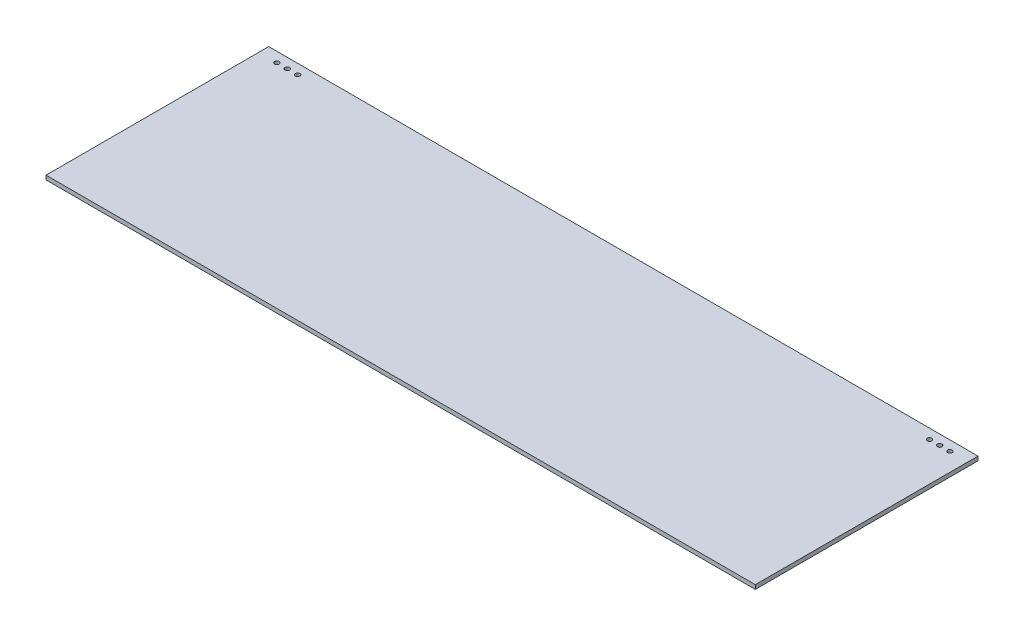
SolidWorks part; units mm, degrees
ref_plane "Front Plane" through (0, 0, 0) normal (0, 0, 1) x (1, 0, 0)
ref_plane "Top Plane" through (0, 0, 0) normal (0, 1, 0) x (1, 0, 0)
ref_plane "Right Plane" through (0, 0, 0) normal (1, 0, 0) x (0, 0, -1)
sketch "Sketch1" plane through (0, 0, 0) normal (0, 0, 1) x (1, 0, 0)
  line L1 (-273.05, -1.5875) -> (273.05, -1.5875)
  line L2 (-273.05, -1.5875) -> (-273.05, 1.5875)
  line L3 (-273.05, 1.5875) -> (273.05, 1.5875)
  line L4 (273.05, -1.5875) -> (273.05, 1.5875)
  line L5 (-273.05, -1.5875) -> (273.05, 1.5875) construction
  line L6 (-273.05, 1.5875) -> (273.05, -1.5875) construction
  point P0 (0, 0)
  dimension "D1" = 3.175
  dimension "D2" = 546.1
extrude "Boss-Extrude1" add sketch "Sketch1" along normal blind 171.45
sketch "Sketch2" plane through (0, 1.5875, 0) normal (0, 1, 0) x (1, 0, 0)
  line L0 (-259.08, -7.62) -> (-251.079, -7.62) construction
  line L1 (-259.08, -7.62) -> (-259.08, -5.842)
  line L2 (-259.08, -5.842) -> (-259.08, -7.62)
  line L3 (-260.858, -7.62) -> (-259.08, -7.62)
  line L4 (273.05, 0) -> (-273.05, 0) construction
  line L5 (-273.05, -171.45) -> (-273.05, 0) construction
  line L6 (0, 0) -> (0, -171.45)
  line L7 (273.05, -171.45) -> (-273.05, -171.45) construction
  line L8 (260.858, -7.62) -> (259.08, -7.62)
  line L9 (259.08, -5.842) -> (259.08, -7.62)
  line L10 (259.08, -7.62) -> (259.08, -5.842)
  circle A5 centre (-259.08, -7.62) radius 1.778
  circle A8 centre (243.332, -7.62) radius 1.778
  circle A9 centre (251.206, -7.62) radius 1.778
  circle A10 centre (259.08, -7.62) radius 1.778
  circle A13 centre (-251.079, -7.62) radius 1.778
  circle A14 centre (-243.078, -7.62) radius 1.778
  dimension "D1" = 5.842
  dimension "D2" = 12.192
  dimension "D4" = 3
  dimension "D3" = 3.556
  dimension "D6" = 8.001
extrude "Cut-Extrude2" cut sketch "Sketch2" against normal through all contours L1 A5 L3 | A10 | A9 | A8 | A5 | A13 | A14 region at (-259.8346, 1.5875, 6.8654)
